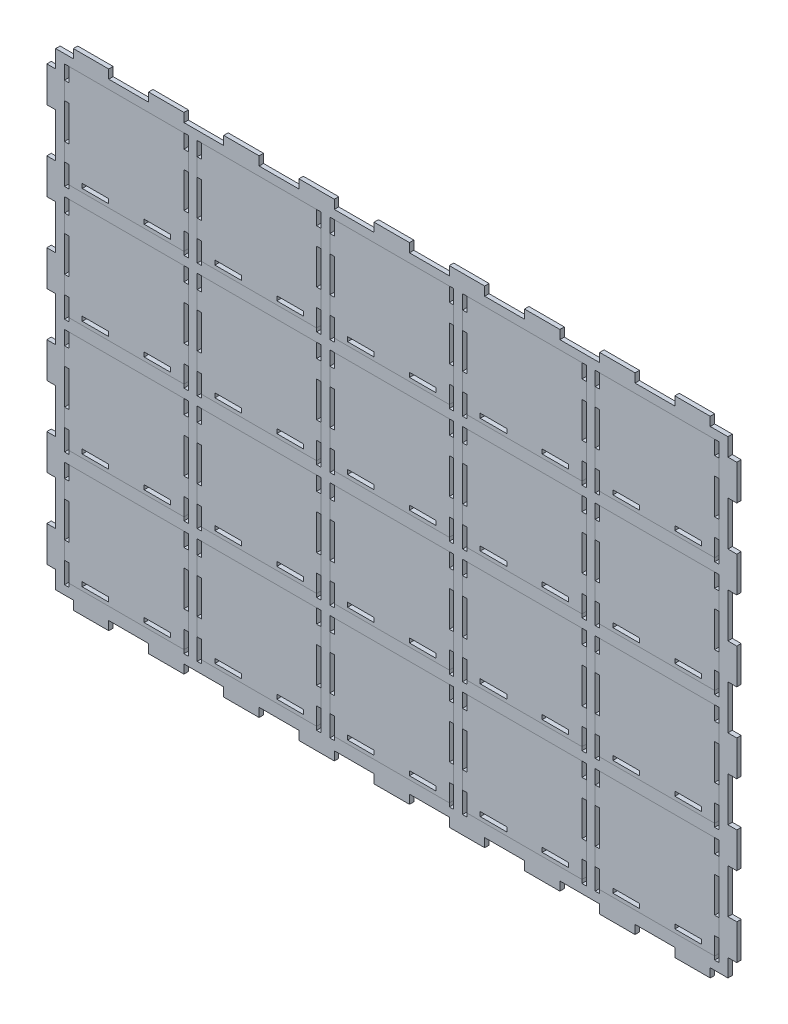
SolidWorks part; units mm, degrees
ref_plane "Front" through (0, 0, 0) normal (0, 0, 1) x (1, 0, 0)
ref_plane "Top" through (0, 0, 0) normal (0, 1, 0) x (1, 0, 0)
ref_plane "Right" through (0, 0, 0) normal (1, 0, 0) x (0, 0, -1)
sketch "Sketch1" plane through (0, 0, 0) normal (0, 0, 1) x (1, 0, 0)
  line L0 (115, 67.5) -> (115, 127.5)
  line L1 (115, 127.5) -> (185, 127.5)
  line L2 (185, 127.5) -> (185, 67.5)
  line L3 (185, 67.5) -> (182.5, 67.5)
  line L4 (182.5, 67.5) -> (182.5, 69.5)
  line L5 (117.5, 69.5) -> (182.5, 69.5)
  line L6 (117.5, 67.5) -> (117.5, 69.5)
  line L7 (117.5, 67.5) -> (115, 67.5)
  line L8 (-190, -132.5) -> (-190, 132.5) construction
  line L9 (-195, -137.5) -> (195, -137.5) construction
  line L10 (-195, -137.5) -> (-195, 137.5) construction
  line L11 (-195, 137.5) -> (195, 137.5) construction
  line L12 (195, -137.5) -> (195, 137.5) construction
  line L13 (-195, -137.5) -> (195, 137.5) construction
  line L14 (-195, 137.5) -> (195, -137.5) construction
  line L15 (-190, 132.5) -> (190, 132.5) construction
  line L16 (190, -132.5) -> (190, 132.5) construction
  line L17 (-190, -132.5) -> (190, -132.5) construction
  line L18 (-180, 137.5) -> (-160, 137.5) construction
  line L19 (-180, 137.5) -> (-180, 132.5)
  line L20 (-180, 132.5) -> (-160, 132.5) construction
  line L21 (-160, 137.5) -> (-160, 132.5)
  line L22 (-180, 137.5) -> (-160, 132.5) construction
  line L23 (-180, 132.5) -> (-160, 137.5) construction
  line L24 (-22.8777, 0) -> (32.9465, 0) construction
  line L25 (0, 22.6378) -> (0, -11.8795) construction
  line L26 (115, 2.5) -> (115, 62.5)
  line L27 (115, 62.5) -> (185, 62.5)
  line L28 (185, 62.5) -> (185, 2.5)
  line L29 (185, 2.5) -> (182.5, 2.5)
  line L30 (182.5, 2.5) -> (182.5, 4.5)
  line L31 (117.5, 4.5) -> (182.5, 4.5)
  line L32 (117.5, 2.5) -> (117.5, 4.5)
  line L33 (117.5, 2.5) -> (115, 2.5)
  line L34 (115, -62.5) -> (115, -2.5)
  line L35 (115, -2.5) -> (185, -2.5)
  line L36 (185, -2.5) -> (185, -62.5)
  line L37 (185, -62.5) -> (182.5, -62.5)
  line L38 (182.5, -62.5) -> (182.5, -60.5)
  line L39 (117.5, -60.5) -> (182.5, -60.5)
  line L40 (117.5, -62.5) -> (117.5, -60.5)
  line L41 (117.5, -62.5) -> (115, -62.5)
  line L42 (115, -127.5) -> (115, -67.5)
  line L43 (115, -67.5) -> (185, -67.5)
  line L44 (185, -67.5) -> (185, -127.5)
  line L45 (185, -127.5) -> (182.5, -127.5)
  line L46 (182.5, -127.5) -> (182.5, -125.5)
  line L47 (117.5, -125.5) -> (182.5, -125.5)
  line L48 (117.5, -127.5) -> (117.5, -125.5)
  line L49 (117.5, -127.5) -> (115, -127.5)
  line L50 (40, 67.5) -> (40, 127.5)
  line L51 (40, 127.5) -> (110, 127.5)
  line L52 (110, 127.5) -> (110, 67.5)
  line L53 (110, 67.5) -> (107.5, 67.5)
  line L54 (107.5, 67.5) -> (107.5, 69.5)
  line L55 (42.5, 69.5) -> (107.5, 69.5)
  line L56 (42.5, 67.5) -> (42.5, 69.5)
  line L57 (42.5, 67.5) -> (40, 67.5)
  line L58 (40, 2.5) -> (40, 62.5)
  line L59 (40, 62.5) -> (110, 62.5)
  line L60 (110, 62.5) -> (110, 2.5)
  line L61 (110, 2.5) -> (107.5, 2.5)
  line L62 (107.5, 2.5) -> (107.5, 4.5)
  line L63 (42.5, 4.5) -> (107.5, 4.5)
  line L64 (42.5, 2.5) -> (42.5, 4.5)
  line L65 (42.5, 2.5) -> (40, 2.5)
  line L66 (40, -62.5) -> (40, -2.5)
  line L67 (40, -2.5) -> (110, -2.5)
  line L68 (110, -2.5) -> (110, -62.5)
  line L69 (110, -62.5) -> (107.5, -62.5)
  line L70 (107.5, -62.5) -> (107.5, -60.5)
  line L71 (42.5, -60.5) -> (107.5, -60.5)
  line L72 (42.5, -62.5) -> (42.5, -60.5)
  line L73 (42.5, -62.5) -> (40, -62.5)
  line L74 (40, -127.5) -> (40, -67.5)
  line L75 (40, -67.5) -> (110, -67.5)
  line L76 (110, -67.5) -> (110, -127.5)
  line L77 (110, -127.5) -> (107.5, -127.5)
  line L78 (107.5, -127.5) -> (107.5, -125.5)
  line L79 (42.5, -125.5) -> (107.5, -125.5)
  line L80 (42.5, -127.5) -> (42.5, -125.5)
  line L81 (42.5, -127.5) -> (40, -127.5)
  line L82 (-35, 67.5) -> (-35, 127.5)
  line L83 (-35, 127.5) -> (35, 127.5)
  line L84 (35, 127.5) -> (35, 67.5)
  line L85 (35, 67.5) -> (32.5, 67.5)
  line L86 (32.5, 67.5) -> (32.5, 69.5)
  line L87 (-32.5, 69.5) -> (32.5, 69.5)
  line L88 (-32.5, 67.5) -> (-32.5, 69.5)
  line L89 (-32.5, 67.5) -> (-35, 67.5)
  line L90 (-35, 2.5) -> (-35, 62.5)
  line L91 (-35, 62.5) -> (35, 62.5)
  line L92 (35, 62.5) -> (35, 2.5)
  line L93 (35, 2.5) -> (32.5, 2.5)
  line L94 (32.5, 2.5) -> (32.5, 4.5)
  line L95 (-32.5, 4.5) -> (32.5, 4.5)
  line L96 (-32.5, 2.5) -> (-32.5, 4.5)
  line L97 (-32.5, 2.5) -> (-35, 2.5)
  line L98 (-35, -62.5) -> (-35, -2.5)
  line L99 (-35, -2.5) -> (35, -2.5)
  line L100 (35, -2.5) -> (35, -62.5)
  line L101 (35, -62.5) -> (32.5, -62.5)
  line L102 (32.5, -62.5) -> (32.5, -60.5)
  line L103 (-32.5, -60.5) -> (32.5, -60.5)
  line L104 (-32.5, -62.5) -> (-32.5, -60.5)
  line L105 (-32.5, -62.5) -> (-35, -62.5)
  line L106 (-35, -127.5) -> (-35, -67.5)
  line L107 (-35, -67.5) -> (35, -67.5)
  line L108 (35, -67.5) -> (35, -127.5)
  line L109 (35, -127.5) -> (32.5, -127.5)
  line L110 (32.5, -127.5) -> (32.5, -125.5)
  line L111 (-32.5, -125.5) -> (32.5, -125.5)
  line L112 (-32.5, -127.5) -> (-32.5, -125.5)
  line L113 (-32.5, -127.5) -> (-35, -127.5)
  line L114 (-110, 67.5) -> (-110, 127.5)
  line L115 (-110, 127.5) -> (-40, 127.5)
  line L116 (-40, 127.5) -> (-40, 67.5)
  line L117 (-40, 67.5) -> (-42.5, 67.5)
  line L118 (-42.5, 67.5) -> (-42.5, 69.5)
  line L119 (-107.5, 69.5) -> (-42.5, 69.5)
  line L120 (-107.5, 67.5) -> (-107.5, 69.5)
  line L121 (-107.5, 67.5) -> (-110, 67.5)
  line L122 (-110, 2.5) -> (-110, 62.5)
  line L123 (-110, 62.5) -> (-40, 62.5)
  line L124 (-40, 62.5) -> (-40, 2.5)
  line L125 (-40, 2.5) -> (-42.5, 2.5)
  line L126 (-42.5, 2.5) -> (-42.5, 4.5)
  line L127 (-107.5, 4.5) -> (-42.5, 4.5)
  line L128 (-107.5, 2.5) -> (-107.5, 4.5)
  line L129 (-107.5, 2.5) -> (-110, 2.5)
  line L130 (-110, -62.5) -> (-110, -2.5)
  line L131 (-110, -2.5) -> (-40, -2.5)
  line L132 (-40, -2.5) -> (-40, -62.5)
  line L133 (-40, -62.5) -> (-42.5, -62.5)
  line L134 (-42.5, -62.5) -> (-42.5, -60.5)
  line L135 (-107.5, -60.5) -> (-42.5, -60.5)
  line L136 (-107.5, -62.5) -> (-107.5, -60.5)
  line L137 (-107.5, -62.5) -> (-110, -62.5)
  line L138 (-110, -127.5) -> (-110, -67.5)
  line L139 (-110, -67.5) -> (-40, -67.5)
  line L140 (-40, -67.5) -> (-40, -127.5)
  line L141 (-40, -127.5) -> (-42.5, -127.5)
  line L142 (-42.5, -127.5) -> (-42.5, -125.5)
  line L143 (-107.5, -125.5) -> (-42.5, -125.5)
  line L144 (-107.5, -127.5) -> (-107.5, -125.5)
  line L145 (-107.5, -127.5) -> (-110, -127.5)
  line L146 (-185, 67.5) -> (-185, 127.5)
  line L147 (-185, 127.5) -> (-115, 127.5)
  line L148 (-115, 127.5) -> (-115, 67.5)
  line L149 (-115, 67.5) -> (-117.5, 67.5)
  line L150 (-117.5, 67.5) -> (-117.5, 69.5)
  line L151 (-182.5, 69.5) -> (-117.5, 69.5)
  line L152 (-182.5, 67.5) -> (-182.5, 69.5)
  line L153 (-182.5, 67.5) -> (-185, 67.5)
  line L154 (-185, 2.5) -> (-185, 62.5)
  line L155 (-185, 62.5) -> (-115, 62.5)
  line L156 (-115, 62.5) -> (-115, 2.5)
  line L157 (-115, 2.5) -> (-117.5, 2.5)
  line L158 (-117.5, 2.5) -> (-117.5, 4.5)
  line L159 (-182.5, 4.5) -> (-117.5, 4.5)
  line L160 (-182.5, 2.5) -> (-182.5, 4.5)
  line L161 (-182.5, 2.5) -> (-185, 2.5)
  line L162 (-185, -62.5) -> (-185, -2.5)
  line L163 (-185, -2.5) -> (-115, -2.5)
  line L164 (-115, -2.5) -> (-115, -62.5)
  line L165 (-115, -62.5) -> (-117.5, -62.5)
  line L166 (-117.5, -62.5) -> (-117.5, -60.5)
  line L167 (-182.5, -60.5) -> (-117.5, -60.5)
  line L168 (-182.5, -62.5) -> (-182.5, -60.5)
  line L169 (-182.5, -62.5) -> (-185, -62.5)
  line L170 (-185, -127.5) -> (-185, -67.5)
  line L171 (-185, -67.5) -> (-115, -67.5)
  line L172 (-115, -67.5) -> (-115, -127.5)
  line L173 (-115, -127.5) -> (-117.5, -127.5)
  line L174 (-117.5, -127.5) -> (-117.5, -125.5)
  line L175 (-182.5, -125.5) -> (-117.5, -125.5)
  line L176 (-182.5, -127.5) -> (-182.5, -125.5)
  line L177 (-182.5, -127.5) -> (-185, -127.5)
  line L178 (-190, 122.5) -> (-195, 122.5)
  line L179 (-190, 122.5) -> (-190, 102.5) construction
  line L180 (-190, 102.5) -> (-195, 102.5)
  line L181 (-195, 122.5) -> (-195, 102.5)
  line L182 (-190, 122.5) -> (-195, 102.5) construction
  line L183 (-190, 102.5) -> (-195, 122.5) construction
  line L184 (190, 102.5) -> (195, 102.5)
  line L185 (195, 122.5) -> (195, 102.5)
  line L186 (190, 122.5) -> (195, 122.5)
  line L187 (-160, 137.5) -> (-180, 137.5)
  line L188 (-160, -137.5) -> (-160, -132.5)
  line L189 (-160, -137.5) -> (-180, -137.5)
  line L190 (-180, -137.5) -> (-180, -132.5)
  line L191 (-117.5, 137.5) -> (-117.5, 132.5)
  line L192 (-117.5, 137.5) -> (-137.5, 137.5)
  line L193 (-137.5, 137.5) -> (-137.5, 132.5)
  line L194 (-117.5, -137.5) -> (-117.5, -132.5)
  line L195 (-117.5, -137.5) -> (-137.5, -137.5)
  line L196 (-137.5, -137.5) -> (-137.5, -132.5)
  line L197 (-75, 137.5) -> (-75, 132.5)
  line L198 (-75, 137.5) -> (-95, 137.5)
  line L199 (-95, 137.5) -> (-95, 132.5)
  line L200 (-75, -137.5) -> (-75, -132.5)
  line L201 (-75, -137.5) -> (-95, -137.5)
  line L202 (-95, -137.5) -> (-95, -132.5)
  line L203 (-32.5, 137.5) -> (-32.5, 132.5)
  line L204 (-32.5, 137.5) -> (-52.5, 137.5)
  line L205 (-52.5, 137.5) -> (-52.5, 132.5)
  line L206 (-32.5, -137.5) -> (-32.5, -132.5)
  line L207 (-32.5, -137.5) -> (-52.5, -137.5)
  line L208 (-52.5, -137.5) -> (-52.5, -132.5)
  line L209 (10, 137.5) -> (10, 132.5)
  line L210 (10, 137.5) -> (-10, 137.5)
  line L211 (-10, 137.5) -> (-10, 132.5)
  line L212 (10, -137.5) -> (10, -132.5)
  line L213 (10, -137.5) -> (-10, -137.5)
  line L214 (-10, -137.5) -> (-10, -132.5)
  line L215 (52.5, 137.5) -> (52.5, 132.5)
  line L216 (52.5, 137.5) -> (32.5, 137.5)
  line L217 (32.5, 137.5) -> (32.5, 132.5)
  line L218 (52.5, -137.5) -> (52.5, -132.5)
  line L219 (52.5, -137.5) -> (32.5, -137.5)
  line L220 (32.5, -137.5) -> (32.5, -132.5)
  line L221 (95, 137.5) -> (95, 132.5)
  line L222 (95, 137.5) -> (75, 137.5)
  line L223 (75, 137.5) -> (75, 132.5)
  line L224 (95, -137.5) -> (95, -132.5)
  line L225 (95, -137.5) -> (75, -137.5)
  line L226 (75, -137.5) -> (75, -132.5)
  line L227 (137.5, 137.5) -> (137.5, 132.5)
  line L228 (137.5, 137.5) -> (117.5, 137.5)
  line L229 (117.5, 137.5) -> (117.5, 132.5)
  line L230 (137.5, -137.5) -> (137.5, -132.5)
  line L231 (137.5, -137.5) -> (117.5, -137.5)
  line L232 (117.5, -137.5) -> (117.5, -132.5)
  line L233 (180, 137.5) -> (180, 132.5)
  line L234 (180, 137.5) -> (160, 137.5)
  line L235 (160, 137.5) -> (160, 132.5)
  line L236 (180, -137.5) -> (180, -132.5)
  line L237 (180, -137.5) -> (160, -137.5)
  line L238 (160, -137.5) -> (160, -132.5)
  line L239 (-190, 77.5) -> (-195, 77.5)
  line L240 (-195, 77.5) -> (-195, 57.5)
  line L241 (-190, 57.5) -> (-195, 57.5)
  line L242 (190, 77.5) -> (195, 77.5)
  line L243 (195, 77.5) -> (195, 57.5)
  line L244 (190, 57.5) -> (195, 57.5)
  line L245 (-190, 32.5) -> (-195, 32.5)
  line L246 (-195, 32.5) -> (-195, 12.5)
  line L247 (-190, 12.5) -> (-195, 12.5)
  line L248 (190, 32.5) -> (195, 32.5)
  line L249 (195, 32.5) -> (195, 12.5)
  line L250 (190, 12.5) -> (195, 12.5)
  line L251 (-190, -12.5) -> (-195, -12.5)
  line L252 (-195, -12.5) -> (-195, -32.5)
  line L253 (-190, -32.5) -> (-195, -32.5)
  line L254 (190, -12.5) -> (195, -12.5)
  line L255 (195, -12.5) -> (195, -32.5)
  line L256 (190, -32.5) -> (195, -32.5)
  line L257 (-190, -57.5) -> (-195, -57.5)
  line L258 (-195, -57.5) -> (-195, -77.5)
  line L259 (-190, -77.5) -> (-195, -77.5)
  line L260 (190, -57.5) -> (195, -57.5)
  line L261 (195, -57.5) -> (195, -77.5)
  line L262 (190, -77.5) -> (195, -77.5)
  line L263 (-190, -102.5) -> (-195, -102.5)
  line L264 (-195, -102.5) -> (-195, -122.5)
  line L265 (-190, -122.5) -> (-195, -122.5)
  line L266 (190, -102.5) -> (195, -102.5)
  line L267 (195, -102.5) -> (195, -122.5)
  line L268 (190, -122.5) -> (195, -122.5)
  line L269 (-180, 132.5) -> (-190, 132.5)
  line L270 (-190, 132.5) -> (-190, 122.5)
  line L271 (-190, -122.5) -> (-190, -132.5)
  line L272 (-190, -132.5) -> (-180, -132.5)
  line L273 (180, -132.5) -> (190, -132.5)
  line L274 (190, -132.5) -> (190, -122.5)
  line L275 (180, 132.5) -> (190, 132.5)
  line L276 (190, 132.5) -> (190, 122.5)
  line L277 (160, 132.5) -> (137.5, 132.5)
  line L278 (160, -132.5) -> (137.5, -132.5)
  line L279 (117.5, -132.5) -> (95, -132.5)
  line L280 (117.5, 132.5) -> (95, 132.5)
  line L281 (75, -132.5) -> (52.5, -132.5)
  line L282 (75, 132.5) -> (52.5, 132.5)
  line L283 (32.5, -132.5) -> (10, -132.5)
  line L284 (32.5, 132.5) -> (10, 132.5)
  line L285 (-10, -132.5) -> (-32.5, -132.5)
  line L286 (-10, 132.5) -> (-32.5, 132.5)
  line L287 (-52.5, -132.5) -> (-75, -132.5)
  line L288 (-52.5, 132.5) -> (-75, 132.5)
  line L289 (-95, -132.5) -> (-117.5, -132.5)
  line L290 (-95, 132.5) -> (-117.5, 132.5)
  line L291 (-137.5, -132.5) -> (-160, -132.5)
  line L292 (-137.5, 132.5) -> (-160, 132.5)
  line L293 (-190, 102.5) -> (-190, 77.5)
  line L294 (190, 102.5) -> (190, 77.5)
  line L295 (190, 57.5) -> (190, 32.5)
  line L296 (-190, 57.5) -> (-190, 32.5)
  line L297 (190, 12.5) -> (190, -12.5)
  line L298 (-190, 12.5) -> (-190, -12.5)
  line L299 (190, -32.5) -> (190, -57.5)
  line L300 (-190, -32.5) -> (-190, -57.5)
  line L301 (190, -77.5) -> (190, -102.5)
  line L302 (-190, -77.5) -> (-190, -102.5)
  line L303 (185, 127.5) -> (115, 67.5) construction
  line L304 (115, 74) -> (185, 74) construction
  line L305 (115, 69.5) -> (185, 69.5) construction
  line L306 (115, 69.5) -> (115, 129.5) construction
  line L307 (115, 129.5) -> (185, 129.5) construction
  line L308 (185, 69.5) -> (185, 129.5) construction
  line L309 (115, 69.5) -> (185, 129.5) construction
  line L310 (115, 129.5) -> (185, 69.5) construction
  line L311 (150, 107.4712) -> (150, 89.903) construction
  line L312 (125, 99.5) -> (175, 99.5) construction
  line L313 (117.5, 129.5) -> (117.5, 69.5) construction
  line L314 (182.5, 129.5) -> (182.5, 69.5) construction
  line L315 (175, 71.5) -> (160, 71.5)
  line L316 (125, 74) -> (140, 74)
  line L317 (125, 74) -> (125, 71.5)
  line L318 (125, 71.5) -> (140, 71.5)
  line L319 (140, 74) -> (140, 71.5)
  line L320 (125, 74) -> (140, 71.5) construction
  line L321 (125, 71.5) -> (140, 74) construction
  line L322 (160, 74) -> (160, 71.5)
  line L323 (175, 74) -> (160, 74)
  line L324 (175, 74) -> (175, 71.5)
  line L325 (117.5, 89.5) -> (117.5, 109.5)
  line L326 (117.5, 109.5) -> (115, 109.5)
  line L327 (115, 109.5) -> (115, 119.5)
  line L328 (115, 119.5) -> (117.5, 119.5)
  line L329 (117.5, 119.5) -> (117.5, 129.5) construction
  line L330 (117.5, 129.5) -> (182.5, 129.5) construction
  line L331 (182.5, 119.5) -> (182.5, 129.5) construction
  line L332 (185, 119.5) -> (182.5, 119.5)
  line L333 (185, 109.5) -> (185, 119.5)
  line L334 (182.5, 109.5) -> (185, 109.5)
  line L335 (182.5, 89.5) -> (182.5, 109.5)
  line L336 (182.5, 89.5) -> (185, 89.5)
  line L337 (185, 89.5) -> (185, 79.5)
  line L338 (185, 79.5) -> (182.5, 79.5)
  line L339 (182.5, 79.5) -> (182.5, 69.5)
  line L340 (117.5, 69.5) -> (182.5, 69.5)
  line L341 (117.5, 79.5) -> (117.5, 69.5)
  line L342 (115, 79.5) -> (117.5, 79.5)
  line L343 (115, 89.5) -> (115, 79.5)
  line L344 (117.5, 89.5) -> (115, 89.5)
  line L345 (117.5, 124.5) -> (117.5, 119.5)
  line L346 (182.5, 124.5) -> (182.5, 119.5)
  line L347 (117.5, 124.5) -> (117.5, 127.5)
  line L348 (182.5, 124.5) -> (182.5, 127.5)
  line L349 (117.5, 127.5) -> (182.5, 127.5)
  line L350 (117.5, 59.5) -> (117.5, 62.5)
  line L351 (117.5, 62.5) -> (182.5, 62.5)
  line L352 (182.5, 59.5) -> (182.5, 62.5)
  line L353 (182.5, 59.5) -> (182.5, 54.5)
  line L354 (185, 54.5) -> (182.5, 54.5)
  line L355 (185, 44.5) -> (185, 54.5)
  line L356 (182.5, 44.5) -> (185, 44.5)
  line L357 (182.5, 24.5) -> (182.5, 44.5)
  line L358 (182.5, 24.5) -> (185, 24.5)
  line L359 (185, 24.5) -> (185, 14.5)
  line L360 (185, 14.5) -> (182.5, 14.5)
  line L361 (182.5, 14.5) -> (182.5, 4.5)
  line L362 (117.5, 4.5) -> (182.5, 4.5)
  line L363 (117.5, 14.5) -> (117.5, 4.5)
  line L364 (115, 14.5) -> (117.5, 14.5)
  line L365 (115, 24.5) -> (115, 14.5)
  line L366 (117.5, 24.5) -> (115, 24.5)
  line L367 (117.5, 24.5) -> (117.5, 44.5)
  line L368 (117.5, 44.5) -> (115, 44.5)
  line L369 (115, 44.5) -> (115, 54.5)
  line L370 (115, 54.5) -> (117.5, 54.5)
  line L371 (117.5, 59.5) -> (117.5, 54.5)
  line L372 (125, 9) -> (140, 9)
  line L373 (140, 9) -> (140, 6.5)
  line L374 (125, 6.5) -> (140, 6.5)
  line L375 (125, 9) -> (125, 6.5)
  line L376 (175, 6.5) -> (160, 6.5)
  line L377 (160, 9) -> (160, 6.5)
  line L378 (175, 9) -> (160, 9)
  line L379 (175, 9) -> (175, 6.5)
  line L380 (117.5, -5.5) -> (117.5, -2.5)
  line L381 (117.5, -2.5) -> (182.5, -2.5)
  line L382 (182.5, -5.5) -> (182.5, -2.5)
  line L383 (182.5, -5.5) -> (182.5, -10.5)
  line L384 (185, -10.5) -> (182.5, -10.5)
  line L385 (185, -20.5) -> (185, -10.5)
  line L386 (182.5, -20.5) -> (185, -20.5)
  line L387 (182.5, -40.5) -> (182.5, -20.5)
  line L388 (182.5, -40.5) -> (185, -40.5)
  line L389 (185, -40.5) -> (185, -50.5)
  line L390 (185, -50.5) -> (182.5, -50.5)
  line L391 (182.5, -50.5) -> (182.5, -60.5)
  line L392 (117.5, -60.5) -> (182.5, -60.5)
  line L393 (117.5, -50.5) -> (117.5, -60.5)
  line L394 (115, -50.5) -> (117.5, -50.5)
  line L395 (115, -40.5) -> (115, -50.5)
  line L396 (117.5, -40.5) -> (115, -40.5)
  line L397 (117.5, -40.5) -> (117.5, -20.5)
  line L398 (117.5, -20.5) -> (115, -20.5)
  line L399 (115, -20.5) -> (115, -10.5)
  line L400 (115, -10.5) -> (117.5, -10.5)
  line L401 (117.5, -5.5) -> (117.5, -10.5)
  line L402 (125, -56) -> (140, -56)
  line L403 (140, -56) -> (140, -58.5)
  line L404 (125, -58.5) -> (140, -58.5)
  line L405 (125, -56) -> (125, -58.5)
  line L406 (175, -58.5) -> (160, -58.5)
  line L407 (160, -56) -> (160, -58.5)
  line L408 (175, -56) -> (160, -56)
  line L409 (175, -56) -> (175, -58.5)
  line L410 (117.5, -70.5) -> (117.5, -67.5)
  line L411 (117.5, -67.5) -> (182.5, -67.5)
  line L412 (182.5, -70.5) -> (182.5, -67.5)
  line L413 (182.5, -70.5) -> (182.5, -75.5)
  line L414 (185, -75.5) -> (182.5, -75.5)
  line L415 (185, -85.5) -> (185, -75.5)
  line L416 (182.5, -85.5) -> (185, -85.5)
  line L417 (182.5, -105.5) -> (182.5, -85.5)
  line L418 (182.5, -105.5) -> (185, -105.5)
  line L419 (185, -105.5) -> (185, -115.5)
  line L420 (185, -115.5) -> (182.5, -115.5)
  line L421 (182.5, -115.5) -> (182.5, -125.5)
  line L422 (117.5, -125.5) -> (182.5, -125.5)
  line L423 (117.5, -115.5) -> (117.5, -125.5)
  line L424 (115, -115.5) -> (117.5, -115.5)
  line L425 (115, -105.5) -> (115, -115.5)
  line L426 (117.5, -105.5) -> (115, -105.5)
  line L427 (117.5, -105.5) -> (117.5, -85.5)
  line L428 (117.5, -85.5) -> (115, -85.5)
  line L429 (115, -85.5) -> (115, -75.5)
  line L430 (115, -75.5) -> (117.5, -75.5)
  line L431 (117.5, -70.5) -> (117.5, -75.5)
  line L432 (125, -121) -> (140, -121)
  line L433 (140, -121) -> (140, -123.5)
  line L434 (125, -123.5) -> (140, -123.5)
  line L435 (125, -121) -> (125, -123.5)
  line L436 (175, -123.5) -> (160, -123.5)
  line L437 (160, -121) -> (160, -123.5)
  line L438 (175, -121) -> (160, -121)
  line L439 (175, -121) -> (175, -123.5)
  line L440 (42.5, 59.5) -> (42.5, 62.5)
  line L441 (42.5, 62.5) -> (107.5, 62.5)
  line L442 (107.5, 59.5) -> (107.5, 62.5)
  line L443 (107.5, 59.5) -> (107.5, 54.5)
  line L444 (110, 54.5) -> (107.5, 54.5)
  line L445 (110, 44.5) -> (110, 54.5)
  line L446 (107.5, 44.5) -> (110, 44.5)
  line L447 (107.5, 24.5) -> (107.5, 44.5)
  line L448 (107.5, 24.5) -> (110, 24.5)
  line L449 (110, 24.5) -> (110, 14.5)
  line L450 (110, 14.5) -> (107.5, 14.5)
  line L451 (107.5, 14.5) -> (107.5, 4.5)
  line L452 (42.5, 4.5) -> (107.5, 4.5)
  line L453 (42.5, 14.5) -> (42.5, 4.5)
  line L454 (40, 14.5) -> (42.5, 14.5)
  line L455 (40, 24.5) -> (40, 14.5)
  line L456 (42.5, 24.5) -> (40, 24.5)
  line L457 (42.5, 24.5) -> (42.5, 44.5)
  line L458 (42.5, 44.5) -> (40, 44.5)
  line L459 (40, 44.5) -> (40, 54.5)
  line L460 (40, 54.5) -> (42.5, 54.5)
  line L461 (42.5, 59.5) -> (42.5, 54.5)
  line L462 (50, 9) -> (65, 9)
  line L463 (65, 9) -> (65, 6.5)
  line L464 (50, 6.5) -> (65, 6.5)
  line L465 (50, 9) -> (50, 6.5)
  line L466 (100, 6.5) -> (85, 6.5)
  line L467 (85, 9) -> (85, 6.5)
  line L468 (100, 9) -> (85, 9)
  line L469 (100, 9) -> (100, 6.5)
  line L470 (42.5, -5.5) -> (42.5, -2.5)
  line L471 (42.5, -2.5) -> (107.5, -2.5)
  line L472 (107.5, -5.5) -> (107.5, -2.5)
  line L473 (107.5, -5.5) -> (107.5, -10.5)
  line L474 (110, -10.5) -> (107.5, -10.5)
  line L475 (110, -20.5) -> (110, -10.5)
  line L476 (107.5, -20.5) -> (110, -20.5)
  line L477 (107.5, -40.5) -> (107.5, -20.5)
  line L478 (107.5, -40.5) -> (110, -40.5)
  line L479 (110, -40.5) -> (110, -50.5)
  line L480 (110, -50.5) -> (107.5, -50.5)
  line L481 (107.5, -50.5) -> (107.5, -60.5)
  line L482 (42.5, -60.5) -> (107.5, -60.5)
  line L483 (42.5, -50.5) -> (42.5, -60.5)
  line L484 (40, -50.5) -> (42.5, -50.5)
  line L485 (40, -40.5) -> (40, -50.5)
  line L486 (42.5, -40.5) -> (40, -40.5)
  line L487 (42.5, -40.5) -> (42.5, -20.5)
  line L488 (42.5, -20.5) -> (40, -20.5)
  line L489 (40, -20.5) -> (40, -10.5)
  line L490 (40, -10.5) -> (42.5, -10.5)
  line L491 (42.5, -5.5) -> (42.5, -10.5)
  line L492 (50, -56) -> (65, -56)
  line L493 (65, -56) -> (65, -58.5)
  line L494 (50, -58.5) -> (65, -58.5)
  line L495 (50, -56) -> (50, -58.5)
  line L496 (100, -58.5) -> (85, -58.5)
  line L497 (85, -56) -> (85, -58.5)
  line L498 (100, -56) -> (85, -56)
  line L499 (100, -56) -> (100, -58.5)
  line L500 (42.5, -70.5) -> (42.5, -67.5)
  line L501 (42.5, -67.5) -> (107.5, -67.5)
  line L502 (107.5, -70.5) -> (107.5, -67.5)
  line L503 (107.5, -70.5) -> (107.5, -75.5)
  line L504 (110, -75.5) -> (107.5, -75.5)
  line L505 (110, -85.5) -> (110, -75.5)
  line L506 (107.5, -85.5) -> (110, -85.5)
  line L507 (107.5, -105.5) -> (107.5, -85.5)
  line L508 (107.5, -105.5) -> (110, -105.5)
  line L509 (110, -105.5) -> (110, -115.5)
  line L510 (110, -115.5) -> (107.5, -115.5)
  line L511 (107.5, -115.5) -> (107.5, -125.5)
  line L512 (42.5, -125.5) -> (107.5, -125.5)
  line L513 (42.5, -115.5) -> (42.5, -125.5)
  line L514 (40, -115.5) -> (42.5, -115.5)
  line L515 (40, -105.5) -> (40, -115.5)
  line L516 (42.5, -105.5) -> (40, -105.5)
  line L517 (42.5, -105.5) -> (42.5, -85.5)
  line L518 (42.5, -85.5) -> (40, -85.5)
  line L519 (40, -85.5) -> (40, -75.5)
  line L520 (40, -75.5) -> (42.5, -75.5)
  line L521 (42.5, -70.5) -> (42.5, -75.5)
  line L522 (50, -121) -> (65, -121)
  line L523 (65, -121) -> (65, -123.5)
  line L524 (50, -123.5) -> (65, -123.5)
  line L525 (50, -121) -> (50, -123.5)
  line L526 (100, -123.5) -> (85, -123.5)
  line L527 (85, -121) -> (85, -123.5)
  line L528 (100, -121) -> (85, -121)
  line L529 (100, -121) -> (100, -123.5)
  line L530 (42.5, 124.5) -> (42.5, 127.5)
  line L531 (42.5, 127.5) -> (107.5, 127.5)
  line L532 (107.5, 124.5) -> (107.5, 127.5)
  line L533 (107.5, 124.5) -> (107.5, 119.5)
  line L534 (110, 119.5) -> (107.5, 119.5)
  line L535 (110, 109.5) -> (110, 119.5)
  line L536 (107.5, 109.5) -> (110, 109.5)
  line L537 (107.5, 89.5) -> (107.5, 109.5)
  line L538 (107.5, 89.5) -> (110, 89.5)
  line L539 (110, 89.5) -> (110, 79.5)
  line L540 (110, 79.5) -> (107.5, 79.5)
  line L541 (107.5, 79.5) -> (107.5, 69.5)
  line L542 (42.5, 69.5) -> (107.5, 69.5)
  line L543 (42.5, 79.5) -> (42.5, 69.5)
  line L544 (40, 79.5) -> (42.5, 79.5)
  line L545 (40, 89.5) -> (40, 79.5)
  line L546 (42.5, 89.5) -> (40, 89.5)
  line L547 (42.5, 89.5) -> (42.5, 109.5)
  line L548 (42.5, 109.5) -> (40, 109.5)
  line L549 (40, 109.5) -> (40, 119.5)
  line L550 (40, 119.5) -> (42.5, 119.5)
  line L551 (42.5, 124.5) -> (42.5, 119.5)
  line L552 (100, 71.5) -> (85, 71.5)
  line L553 (85, 74) -> (85, 71.5)
  line L554 (100, 74) -> (85, 74)
  line L555 (100, 74) -> (100, 71.5)
  line L556 (50, 74) -> (65, 74)
  line L557 (65, 74) -> (65, 71.5)
  line L558 (50, 71.5) -> (65, 71.5)
  line L559 (50, 74) -> (50, 71.5)
  line L560 (-32.5, 59.5) -> (-32.5, 62.5)
  line L561 (-32.5, 62.5) -> (32.5, 62.5)
  line L562 (32.5, 59.5) -> (32.5, 62.5)
  line L563 (32.5, 59.5) -> (32.5, 54.5)
  line L564 (35, 54.5) -> (32.5, 54.5)
  line L565 (35, 44.5) -> (35, 54.5)
  line L566 (32.5, 44.5) -> (35, 44.5)
  line L567 (32.5, 24.5) -> (32.5, 44.5)
  line L568 (32.5, 24.5) -> (35, 24.5)
  line L569 (35, 24.5) -> (35, 14.5)
  line L570 (35, 14.5) -> (32.5, 14.5)
  line L571 (32.5, 14.5) -> (32.5, 4.5)
  line L572 (-32.5, 4.5) -> (32.5, 4.5)
  line L573 (-32.5, 14.5) -> (-32.5, 4.5)
  line L574 (-35, 14.5) -> (-32.5, 14.5)
  line L575 (-35, 24.5) -> (-35, 14.5)
  line L576 (-32.5, 24.5) -> (-35, 24.5)
  line L577 (-32.5, 24.5) -> (-32.5, 44.5)
  line L578 (-32.5, 44.5) -> (-35, 44.5)
  line L579 (-35, 44.5) -> (-35, 54.5)
  line L580 (-35, 54.5) -> (-32.5, 54.5)
  line L581 (-32.5, 59.5) -> (-32.5, 54.5)
  line L582 (-25, 9) -> (-10, 9)
  line L583 (-10, 9) -> (-10, 6.5)
  line L584 (-25, 6.5) -> (-10, 6.5)
  line L585 (-25, 9) -> (-25, 6.5)
  line L586 (25, 6.5) -> (10, 6.5)
  line L587 (10, 9) -> (10, 6.5)
  line L588 (25, 9) -> (10, 9)
  line L589 (25, 9) -> (25, 6.5)
  line L590 (-32.5, -5.5) -> (-32.5, -2.5)
  line L591 (-32.5, -2.5) -> (32.5, -2.5)
  line L592 (32.5, -5.5) -> (32.5, -2.5)
  line L593 (32.5, -5.5) -> (32.5, -10.5)
  line L594 (35, -10.5) -> (32.5, -10.5)
  line L595 (35, -20.5) -> (35, -10.5)
  line L596 (32.5, -20.5) -> (35, -20.5)
  line L597 (32.5, -40.5) -> (32.5, -20.5)
  line L598 (32.5, -40.5) -> (35, -40.5)
  line L599 (35, -40.5) -> (35, -50.5)
  line L600 (35, -50.5) -> (32.5, -50.5)
  line L601 (32.5, -50.5) -> (32.5, -60.5)
  line L602 (-32.5, -60.5) -> (32.5, -60.5)
  line L603 (-32.5, -50.5) -> (-32.5, -60.5)
  line L604 (-35, -50.5) -> (-32.5, -50.5)
  line L605 (-35, -40.5) -> (-35, -50.5)
  line L606 (-32.5, -40.5) -> (-35, -40.5)
  line L607 (-32.5, -40.5) -> (-32.5, -20.5)
  line L608 (-32.5, -20.5) -> (-35, -20.5)
  line L609 (-35, -20.5) -> (-35, -10.5)
  line L610 (-35, -10.5) -> (-32.5, -10.5)
  line L611 (-32.5, -5.5) -> (-32.5, -10.5)
  line L612 (-25, -56) -> (-10, -56)
  line L613 (-10, -56) -> (-10, -58.5)
  line L614 (-25, -58.5) -> (-10, -58.5)
  line L615 (-25, -56) -> (-25, -58.5)
  line L616 (25, -58.5) -> (10, -58.5)
  line L617 (10, -56) -> (10, -58.5)
  line L618 (25, -56) -> (10, -56)
  line L619 (25, -56) -> (25, -58.5)
  line L620 (-32.5, -70.5) -> (-32.5, -67.5)
  line L621 (-32.5, -67.5) -> (32.5, -67.5)
  line L622 (32.5, -70.5) -> (32.5, -67.5)
  line L623 (32.5, -70.5) -> (32.5, -75.5)
  line L624 (35, -75.5) -> (32.5, -75.5)
  line L625 (35, -85.5) -> (35, -75.5)
  line L626 (32.5, -85.5) -> (35, -85.5)
  line L627 (32.5, -105.5) -> (32.5, -85.5)
  line L628 (32.5, -105.5) -> (35, -105.5)
  line L629 (35, -105.5) -> (35, -115.5)
  line L630 (35, -115.5) -> (32.5, -115.5)
  line L631 (32.5, -115.5) -> (32.5, -125.5)
  line L632 (-32.5, -125.5) -> (32.5, -125.5)
  line L633 (-32.5, -115.5) -> (-32.5, -125.5)
  line L634 (-35, -115.5) -> (-32.5, -115.5)
  line L635 (-35, -105.5) -> (-35, -115.5)
  line L636 (-32.5, -105.5) -> (-35, -105.5)
  line L637 (-32.5, -105.5) -> (-32.5, -85.5)
  line L638 (-32.5, -85.5) -> (-35, -85.5)
  line L639 (-35, -85.5) -> (-35, -75.5)
  line L640 (-35, -75.5) -> (-32.5, -75.5)
  line L641 (-32.5, -70.5) -> (-32.5, -75.5)
  line L642 (-25, -121) -> (-10, -121)
  line L643 (-10, -121) -> (-10, -123.5)
  line L644 (-25, -123.5) -> (-10, -123.5)
  line L645 (-25, -121) -> (-25, -123.5)
  line L646 (25, -123.5) -> (10, -123.5)
  line L647 (10, -121) -> (10, -123.5)
  line L648 (25, -121) -> (10, -121)
  line L649 (25, -121) -> (25, -123.5)
  line L650 (-32.5, 124.5) -> (-32.5, 127.5)
  line L651 (-32.5, 127.5) -> (32.5, 127.5)
  line L652 (32.5, 124.5) -> (32.5, 127.5)
  line L653 (32.5, 124.5) -> (32.5, 119.5)
  line L654 (35, 119.5) -> (32.5, 119.5)
  line L655 (35, 109.5) -> (35, 119.5)
  line L656 (32.5, 109.5) -> (35, 109.5)
  line L657 (32.5, 89.5) -> (32.5, 109.5)
  line L658 (32.5, 89.5) -> (35, 89.5)
  line L659 (35, 89.5) -> (35, 79.5)
  line L660 (35, 79.5) -> (32.5, 79.5)
  line L661 (32.5, 79.5) -> (32.5, 69.5)
  line L662 (-32.5, 69.5) -> (32.5, 69.5)
  line L663 (-32.5, 79.5) -> (-32.5, 69.5)
  line L664 (-35, 79.5) -> (-32.5, 79.5)
  line L665 (-35, 89.5) -> (-35, 79.5)
  line L666 (-32.5, 89.5) -> (-35, 89.5)
  line L667 (-32.5, 89.5) -> (-32.5, 109.5)
  line L668 (-32.5, 109.5) -> (-35, 109.5)
  line L669 (-35, 109.5) -> (-35, 119.5)
  line L670 (-35, 119.5) -> (-32.5, 119.5)
  line L671 (-32.5, 124.5) -> (-32.5, 119.5)
  line L672 (25, 71.5) -> (10, 71.5)
  line L673 (10, 74) -> (10, 71.5)
  line L674 (25, 74) -> (10, 74)
  line L675 (25, 74) -> (25, 71.5)
  line L676 (-25, 74) -> (-10, 74)
  line L677 (-10, 74) -> (-10, 71.5)
  line L678 (-25, 71.5) -> (-10, 71.5)
  line L679 (-25, 74) -> (-25, 71.5)
  line L680 (-107.5, 59.5) -> (-107.5, 62.5)
  line L681 (-107.5, 62.5) -> (-42.5, 62.5)
  line L682 (-42.5, 59.5) -> (-42.5, 62.5)
  line L683 (-42.5, 59.5) -> (-42.5, 54.5)
  line L684 (-40, 54.5) -> (-42.5, 54.5)
  line L685 (-40, 44.5) -> (-40, 54.5)
  line L686 (-42.5, 44.5) -> (-40, 44.5)
  line L687 (-42.5, 24.5) -> (-42.5, 44.5)
  line L688 (-42.5, 24.5) -> (-40, 24.5)
  line L689 (-40, 24.5) -> (-40, 14.5)
  line L690 (-40, 14.5) -> (-42.5, 14.5)
  line L691 (-42.5, 14.5) -> (-42.5, 4.5)
  line L692 (-107.5, 4.5) -> (-42.5, 4.5)
  line L693 (-107.5, 14.5) -> (-107.5, 4.5)
  line L694 (-110, 14.5) -> (-107.5, 14.5)
  line L695 (-110, 24.5) -> (-110, 14.5)
  line L696 (-107.5, 24.5) -> (-110, 24.5)
  line L697 (-107.5, 24.5) -> (-107.5, 44.5)
  line L698 (-107.5, 44.5) -> (-110, 44.5)
  line L699 (-110, 44.5) -> (-110, 54.5)
  line L700 (-110, 54.5) -> (-107.5, 54.5)
  line L701 (-107.5, 59.5) -> (-107.5, 54.5)
  line L702 (-100, 9) -> (-85, 9)
  line L703 (-85, 9) -> (-85, 6.5)
  line L704 (-100, 6.5) -> (-85, 6.5)
  line L705 (-100, 9) -> (-100, 6.5)
  line L706 (-50, 6.5) -> (-65, 6.5)
  line L707 (-65, 9) -> (-65, 6.5)
  line L708 (-50, 9) -> (-65, 9)
  line L709 (-50, 9) -> (-50, 6.5)
  line L710 (-107.5, -5.5) -> (-107.5, -2.5)
  line L711 (-107.5, -2.5) -> (-42.5, -2.5)
  line L712 (-42.5, -5.5) -> (-42.5, -2.5)
  line L713 (-42.5, -5.5) -> (-42.5, -10.5)
  line L714 (-40, -10.5) -> (-42.5, -10.5)
  line L715 (-40, -20.5) -> (-40, -10.5)
  line L716 (-42.5, -20.5) -> (-40, -20.5)
  line L717 (-42.5, -40.5) -> (-42.5, -20.5)
  line L718 (-42.5, -40.5) -> (-40, -40.5)
  line L719 (-40, -40.5) -> (-40, -50.5)
  line L720 (-40, -50.5) -> (-42.5, -50.5)
  line L721 (-42.5, -50.5) -> (-42.5, -60.5)
  line L722 (-107.5, -60.5) -> (-42.5, -60.5)
  line L723 (-107.5, -50.5) -> (-107.5, -60.5)
  line L724 (-110, -50.5) -> (-107.5, -50.5)
  line L725 (-110, -40.5) -> (-110, -50.5)
  line L726 (-107.5, -40.5) -> (-110, -40.5)
  line L727 (-107.5, -40.5) -> (-107.5, -20.5)
  line L728 (-107.5, -20.5) -> (-110, -20.5)
  line L729 (-110, -20.5) -> (-110, -10.5)
  line L730 (-110, -10.5) -> (-107.5, -10.5)
  line L731 (-107.5, -5.5) -> (-107.5, -10.5)
  line L732 (-100, -56) -> (-85, -56)
  line L733 (-85, -56) -> (-85, -58.5)
  line L734 (-100, -58.5) -> (-85, -58.5)
  line L735 (-100, -56) -> (-100, -58.5)
  line L736 (-50, -58.5) -> (-65, -58.5)
  line L737 (-65, -56) -> (-65, -58.5)
  line L738 (-50, -56) -> (-65, -56)
  line L739 (-50, -56) -> (-50, -58.5)
  line L740 (-107.5, -70.5) -> (-107.5, -67.5)
  line L741 (-107.5, -67.5) -> (-42.5, -67.5)
  line L742 (-42.5, -70.5) -> (-42.5, -67.5)
  line L743 (-42.5, -70.5) -> (-42.5, -75.5)
  line L744 (-40, -75.5) -> (-42.5, -75.5)
  line L745 (-40, -85.5) -> (-40, -75.5)
  line L746 (-42.5, -85.5) -> (-40, -85.5)
  line L747 (-42.5, -105.5) -> (-42.5, -85.5)
  line L748 (-42.5, -105.5) -> (-40, -105.5)
  line L749 (-40, -105.5) -> (-40, -115.5)
  line L750 (-40, -115.5) -> (-42.5, -115.5)
  line L751 (-42.5, -115.5) -> (-42.5, -125.5)
  line L752 (-107.5, -125.5) -> (-42.5, -125.5)
  line L753 (-107.5, -115.5) -> (-107.5, -125.5)
  line L754 (-110, -115.5) -> (-107.5, -115.5)
  line L755 (-110, -105.5) -> (-110, -115.5)
  line L756 (-107.5, -105.5) -> (-110, -105.5)
  line L757 (-107.5, -105.5) -> (-107.5, -85.5)
  line L758 (-107.5, -85.5) -> (-110, -85.5)
  line L759 (-110, -85.5) -> (-110, -75.5)
  line L760 (-110, -75.5) -> (-107.5, -75.5)
  line L761 (-107.5, -70.5) -> (-107.5, -75.5)
  line L762 (-100, -121) -> (-85, -121)
  line L763 (-85, -121) -> (-85, -123.5)
  line L764 (-100, -123.5) -> (-85, -123.5)
  line L765 (-100, -121) -> (-100, -123.5)
  line L766 (-50, -123.5) -> (-65, -123.5)
  line L767 (-65, -121) -> (-65, -123.5)
  line L768 (-50, -121) -> (-65, -121)
  line L769 (-50, -121) -> (-50, -123.5)
  line L770 (-107.5, 124.5) -> (-107.5, 127.5)
  line L771 (-107.5, 127.5) -> (-42.5, 127.5)
  line L772 (-42.5, 124.5) -> (-42.5, 127.5)
  line L773 (-42.5, 124.5) -> (-42.5, 119.5)
  line L774 (-40, 119.5) -> (-42.5, 119.5)
  line L775 (-40, 109.5) -> (-40, 119.5)
  line L776 (-42.5, 109.5) -> (-40, 109.5)
  line L777 (-42.5, 89.5) -> (-42.5, 109.5)
  line L778 (-42.5, 89.5) -> (-40, 89.5)
  line L779 (-40, 89.5) -> (-40, 79.5)
  line L780 (-40, 79.5) -> (-42.5, 79.5)
  line L781 (-42.5, 79.5) -> (-42.5, 69.5)
  line L782 (-107.5, 69.5) -> (-42.5, 69.5)
  line L783 (-107.5, 79.5) -> (-107.5, 69.5)
  line L784 (-110, 79.5) -> (-107.5, 79.5)
  line L785 (-110, 89.5) -> (-110, 79.5)
  line L786 (-107.5, 89.5) -> (-110, 89.5)
  line L787 (-107.5, 89.5) -> (-107.5, 109.5)
  line L788 (-107.5, 109.5) -> (-110, 109.5)
  line L789 (-110, 109.5) -> (-110, 119.5)
  line L790 (-110, 119.5) -> (-107.5, 119.5)
  line L791 (-107.5, 124.5) -> (-107.5, 119.5)
  line L792 (-50, 71.5) -> (-65, 71.5)
  line L793 (-65, 74) -> (-65, 71.5)
  line L794 (-50, 74) -> (-65, 74)
  line L795 (-50, 74) -> (-50, 71.5)
  line L796 (-100, 74) -> (-85, 74)
  line L797 (-85, 74) -> (-85, 71.5)
  line L798 (-100, 71.5) -> (-85, 71.5)
  line L799 (-100, 74) -> (-100, 71.5)
  line L800 (-182.5, 59.5) -> (-182.5, 62.5)
  line L801 (-182.5, 62.5) -> (-117.5, 62.5)
  line L802 (-117.5, 59.5) -> (-117.5, 62.5)
  line L803 (-117.5, 59.5) -> (-117.5, 54.5)
  line L804 (-115, 54.5) -> (-117.5, 54.5)
  line L805 (-115, 44.5) -> (-115, 54.5)
  line L806 (-117.5, 44.5) -> (-115, 44.5)
  line L807 (-117.5, 24.5) -> (-117.5, 44.5)
  line L808 (-117.5, 24.5) -> (-115, 24.5)
  line L809 (-115, 24.5) -> (-115, 14.5)
  line L810 (-115, 14.5) -> (-117.5, 14.5)
  line L811 (-117.5, 14.5) -> (-117.5, 4.5)
  line L812 (-182.5, 4.5) -> (-117.5, 4.5)
  line L813 (-182.5, 14.5) -> (-182.5, 4.5)
  line L814 (-185, 14.5) -> (-182.5, 14.5)
  line L815 (-185, 24.5) -> (-185, 14.5)
  line L816 (-182.5, 24.5) -> (-185, 24.5)
  line L817 (-182.5, 24.5) -> (-182.5, 44.5)
  line L818 (-182.5, 44.5) -> (-185, 44.5)
  line L819 (-185, 44.5) -> (-185, 54.5)
  line L820 (-185, 54.5) -> (-182.5, 54.5)
  line L821 (-182.5, 59.5) -> (-182.5, 54.5)
  line L822 (-175, 9) -> (-160, 9)
  line L823 (-160, 9) -> (-160, 6.5)
  line L824 (-175, 6.5) -> (-160, 6.5)
  line L825 (-175, 9) -> (-175, 6.5)
  line L826 (-125, 6.5) -> (-140, 6.5)
  line L827 (-140, 9) -> (-140, 6.5)
  line L828 (-125, 9) -> (-140, 9)
  line L829 (-125, 9) -> (-125, 6.5)
  line L830 (-182.5, -5.5) -> (-182.5, -2.5)
  line L831 (-182.5, -2.5) -> (-117.5, -2.5)
  line L832 (-117.5, -5.5) -> (-117.5, -2.5)
  line L833 (-117.5, -5.5) -> (-117.5, -10.5)
  line L834 (-115, -10.5) -> (-117.5, -10.5)
  line L835 (-115, -20.5) -> (-115, -10.5)
  line L836 (-117.5, -20.5) -> (-115, -20.5)
  line L837 (-117.5, -40.5) -> (-117.5, -20.5)
  line L838 (-117.5, -40.5) -> (-115, -40.5)
  line L839 (-115, -40.5) -> (-115, -50.5)
  line L840 (-115, -50.5) -> (-117.5, -50.5)
  line L841 (-117.5, -50.5) -> (-117.5, -60.5)
  line L842 (-182.5, -60.5) -> (-117.5, -60.5)
  line L843 (-182.5, -50.5) -> (-182.5, -60.5)
  line L844 (-185, -50.5) -> (-182.5, -50.5)
  line L845 (-185, -40.5) -> (-185, -50.5)
  line L846 (-182.5, -40.5) -> (-185, -40.5)
  line L847 (-182.5, -40.5) -> (-182.5, -20.5)
  line L848 (-182.5, -20.5) -> (-185, -20.5)
  line L849 (-185, -20.5) -> (-185, -10.5)
  line L850 (-185, -10.5) -> (-182.5, -10.5)
  line L851 (-182.5, -5.5) -> (-182.5, -10.5)
  line L852 (-175, -56) -> (-160, -56)
  line L853 (-160, -56) -> (-160, -58.5)
  line L854 (-175, -58.5) -> (-160, -58.5)
  line L855 (-175, -56) -> (-175, -58.5)
  line L856 (-125, -58.5) -> (-140, -58.5)
  line L857 (-140, -56) -> (-140, -58.5)
  line L858 (-125, -56) -> (-140, -56)
  line L859 (-125, -56) -> (-125, -58.5)
  line L860 (-182.5, -70.5) -> (-182.5, -67.5)
  line L861 (-182.5, -67.5) -> (-117.5, -67.5)
  line L862 (-117.5, -70.5) -> (-117.5, -67.5)
  line L863 (-117.5, -70.5) -> (-117.5, -75.5)
  line L864 (-115, -75.5) -> (-117.5, -75.5)
  line L865 (-115, -85.5) -> (-115, -75.5)
  line L866 (-117.5, -85.5) -> (-115, -85.5)
  line L867 (-117.5, -105.5) -> (-117.5, -85.5)
  line L868 (-117.5, -105.5) -> (-115, -105.5)
  line L869 (-115, -105.5) -> (-115, -115.5)
  line L870 (-115, -115.5) -> (-117.5, -115.5)
  line L871 (-117.5, -115.5) -> (-117.5, -125.5)
  line L872 (-182.5, -125.5) -> (-117.5, -125.5)
  line L873 (-182.5, -115.5) -> (-182.5, -125.5)
  line L874 (-185, -115.5) -> (-182.5, -115.5)
  line L875 (-185, -105.5) -> (-185, -115.5)
  line L876 (-182.5, -105.5) -> (-185, -105.5)
  line L877 (-182.5, -105.5) -> (-182.5, -85.5)
  line L878 (-182.5, -85.5) -> (-185, -85.5)
  line L879 (-185, -85.5) -> (-185, -75.5)
  line L880 (-185, -75.5) -> (-182.5, -75.5)
  line L881 (-182.5, -70.5) -> (-182.5, -75.5)
  line L882 (-175, -121) -> (-160, -121)
  line L883 (-160, -121) -> (-160, -123.5)
  line L884 (-175, -123.5) -> (-160, -123.5)
  line L885 (-175, -121) -> (-175, -123.5)
  line L886 (-125, -123.5) -> (-140, -123.5)
  line L887 (-140, -121) -> (-140, -123.5)
  line L888 (-125, -121) -> (-140, -121)
  line L889 (-125, -121) -> (-125, -123.5)
  line L890 (-182.5, 124.5) -> (-182.5, 127.5)
  line L891 (-182.5, 127.5) -> (-117.5, 127.5)
  line L892 (-117.5, 124.5) -> (-117.5, 127.5)
  line L893 (-117.5, 124.5) -> (-117.5, 119.5)
  line L894 (-115, 119.5) -> (-117.5, 119.5)
  line L895 (-115, 109.5) -> (-115, 119.5)
  line L896 (-117.5, 109.5) -> (-115, 109.5)
  line L897 (-117.5, 89.5) -> (-117.5, 109.5)
  line L898 (-117.5, 89.5) -> (-115, 89.5)
  line L899 (-115, 89.5) -> (-115, 79.5)
  line L900 (-115, 79.5) -> (-117.5, 79.5)
  line L901 (-117.5, 79.5) -> (-117.5, 69.5)
  line L902 (-182.5, 69.5) -> (-117.5, 69.5)
  line L903 (-182.5, 79.5) -> (-182.5, 69.5)
  line L904 (-185, 79.5) -> (-182.5, 79.5)
  line L905 (-185, 89.5) -> (-185, 79.5)
  line L906 (-182.5, 89.5) -> (-185, 89.5)
  line L907 (-182.5, 89.5) -> (-182.5, 109.5)
  line L908 (-182.5, 109.5) -> (-185, 109.5)
  line L909 (-185, 109.5) -> (-185, 119.5)
  line L910 (-185, 119.5) -> (-182.5, 119.5)
  line L911 (-182.5, 124.5) -> (-182.5, 119.5)
  line L912 (-125, 71.5) -> (-140, 71.5)
  line L913 (-140, 74) -> (-140, 71.5)
  line L914 (-125, 74) -> (-140, 74)
  line L915 (-125, 74) -> (-125, 71.5)
  line L916 (-175, 74) -> (-160, 74)
  line L917 (-160, 74) -> (-160, 71.5)
  line L918 (-175, 71.5) -> (-160, 71.5)
  line L919 (-175, 74) -> (-175, 71.5)
  line L920 (115, 127.5) -> (185, 67.5) construction
  line L921 (173.9604, 129.5) -> (185, 129.5) construction
  line L922 (185, 129.5) -> (185, 127.5) construction
  point P8 (0, 0)
  point P21 (-170, 135)
  point P26 (183.75, 67.5)
  point P185 (-192.5, 112.5)
  point P296 (150, 99.5)
  point P313 (150, 129.5)
  point P325 (182.5, 99.5)
  point P328 (132.5, 72.75)
  point P329 (125, 72.75)
  point P340 (117.5, 99.5)
  point P344 (150, 97.5)
  dimension "D1" = 275
  dimension "D2" = 390
  dimension "D3" = 5
  dimension "D4" = 5
  dimension "D5" = 20
  dimension "D6" = 15
  dimension "D7" = 70
  dimension "D8" = 60
  dimension "D9" = 5
  dimension "D10" = 5
  dimension "D11" = 2.5
  dimension "D12" = 2
  dimension "D13" = 15
  dimension "D14" = 15
  dimension "D15" = 15
  dimension "D16" = 60
  dimension "D17" = 70
  dimension "D18" = 4.5
  dimension "D19" = 15
  dimension "D20" = 10
  dimension "D21" = 2.5
  dimension "D22" = 2.5
  dimension "D23" = 10
  dimension "D24" = 10
  dimension "D27" = 2
  dimension "D25" = 4
  dimension "D26" = 5
extrude "Boss-Extrude1" add sketch "Sketch1" along normal blind 2.5 contours L259 L302 L263 L264 L265 L271 L272 L190 L189 L188 L291 L196 L195 L194 L289 L202 L201 L200 L287 L208 L207 L206 L285 L214 L213 L212 L283 L220 L219 L218 L281 L226 L225 L224 L279 L232 L231 L230 L278 L238 L237 L236 L273 L274 L268 L267 L266 L301 L262 L261 L260 region at (-170, 132.7279, 0)
extrude "Boss-Extrude2" add sketch "Sketch1<3>" along normal blind 2.5 separate body contours L830 L851 L850 L162 L848 L847 L846 L844 L843 L167 L841 L840 L164 L838 L837 L836 L834 L833 L832 L163 L855 L852 L853 L854 L858 L859 L856 L857 | L800 L821 L820 L154 L818 L817 L816 L814 L813 L159 L811 L810 L156 L808 L807 L806 L804 L803 L802 L155 L825 L822 L823 L824 L828 L829 L826 L827 | L890 L911 L910 L146 L908 L907 L906 L904 L903 L151 L901 L900 L148 L898 L897 L896 L894 L893 L892 L147 L919 L916 L917 L918 L914 L915 L912 L913 | L770 L791 L790 L114 L788 L787 L786 L784 L783 L119 L781 L780 L116 L778 L777 L776 L774 L773 L772 L115 L799 L796 L797 L798 L794 L795 L792 L793 | L650 L671 L670 L82 L668 L667 L666 L664 L663 L87 L661 L660 L84 L658 L657 L656 L654 L653 L652 L83 L679 L676 L677 L678 L674 L675 L672 L673 | L530 L551 L550 L50 L548 L547 L546 L544 L543 L55 L541 L540 L52 L538 L537 L536 L534 L533 L532 L51 L559 L556 L557 L558 L554 L555 L552 L553 | L346 L348 L1 L347 L345 L328 L0 L326 L325 L344 L342 L341 L5 L339 L338 L2 L336 L335 L334 L332 L316 L319 L318 L317 L323 L324 L315 L322 | L350 L371 L370 L26 L368 L367 L366 L364 L363 L31 L361 L360 L28 L358 L357 L356 L354 L353 L352 L27 L375 L372 L373 L374 L378 L379 L376 L377 | L440 L461 L460 L58 L458 L457 L456 L454 L453 L63 L451 L450 L60 L448 L447 L446 L444 L443 L442 L59 L465 L462 L463 L464 L468 L469 L466 L467 | L560 L581 L580 L90 L578 L577 L576 L574 L573 L95 L571 L570 L92 L568 L567 L566 L564 L563 L562 L91 L585 L582 L583 L584 L588 L589 L586 L587 | L680 L701 L700 L122 L698 L697 L696 L694 L693 L127 L691 L690 L124 L688 L687 L686 L684 L683 L682 L123 L705 L702 L703 L704 L708 L709 L706 L707 | L710 L731 L730 L130 L728 L727 L726 L724 L723 L135 L721 L720 L132 L718 L717 L716 L714 L713 L712 L131 L735 L732 L733 L734 L738 L739 L736 L737 | L590 L611 L610 L98 L608 L607 L606 L604 L603 L103 L601 L600 L100 L598 L597 L596 L594 L593 L592 L99 L615 L612 L613 L614 L618 L619 L616 L617 | L470 L491 L490 L66 L488 L487 L486 L484 L483 L71 L481 L480 L68 L478 L477 L476 L474 L473 L472 L67 L495 L492 L493 L494 L498 L499 L496 L497 | L380 L401 L400 L34 L398 L397 L396 L394 L393 L39 L391 L390 L36 L388 L387 L386 L384 L383 L382 L35 L405 L402 L403 L404 L408 L409 L406 L407 | L410 L431 L430 L42 L428 L427 L426 L424 L423 L47 L421 L420 L44 L418 L417 L416 L414 L413 L412 L43 L435 L432 L433 L434 L438 L439 L436 L437 | L500 L521 L520 L74 L518 L517 L516 L514 L513 L79 L511 L510 L76 L508 L507 L506 L504 L503 L502 L75 L525 L522 L523 L524 L528 L529 L526 L527 | L620 L641 L640 L106 L638 L637 L636 L634 L633 L111 L631 L630 L108 L628 L627 L626 L624 L623 L622 L107 L645 L642 L643 L644 L648 L649 L646 L647 | L740 L761 L760 L138 L758 L757 L756 L754 L753 L143 L751 L750 L140 L748 L747 L746 L744 L743 L742 L139 L765 L762 L763 L764 L768 L769 L766 L767 | L860 L881 L880 L170 L878 L877 L876 L874 L873 L175 L871 L870 L172 L868 L867 L866 L864 L863 L862 L171 L885 L882 L883 L884 L888 L889 L886 L887 region at (150, 99.0352, 0) region at (150, 34.0352, 0) region at (150, -30.9648, 0) region at (150, -95.9648, 0) region at (75, 99.0352, 0) region at (75, 34.0352, 0) region at (75, -30.9648, 0) region at (75, -95.9648, 0) region at (0, 99.0352, 0) region at (0, 34.0352, 0) region at (0, -30.9648, 0) region at (0, -95.9648, 0) region at (-75, 99.0352, 0) region at (-75, 34.0352, 0) region at (-75, -30.9648, 0) region at (-75, -95.9648, 0) region at (-150, 99.0352, 0) region at (-150, 34.0352, 0) region at (-150, -30.9648, 0) region at (-150, -95.9648, 0)
sketch "Sketch1<3>" plane through (0, 0, 0) normal (0, 0, 1) x (1, 0, 0) same geometry as "Sketch1"
